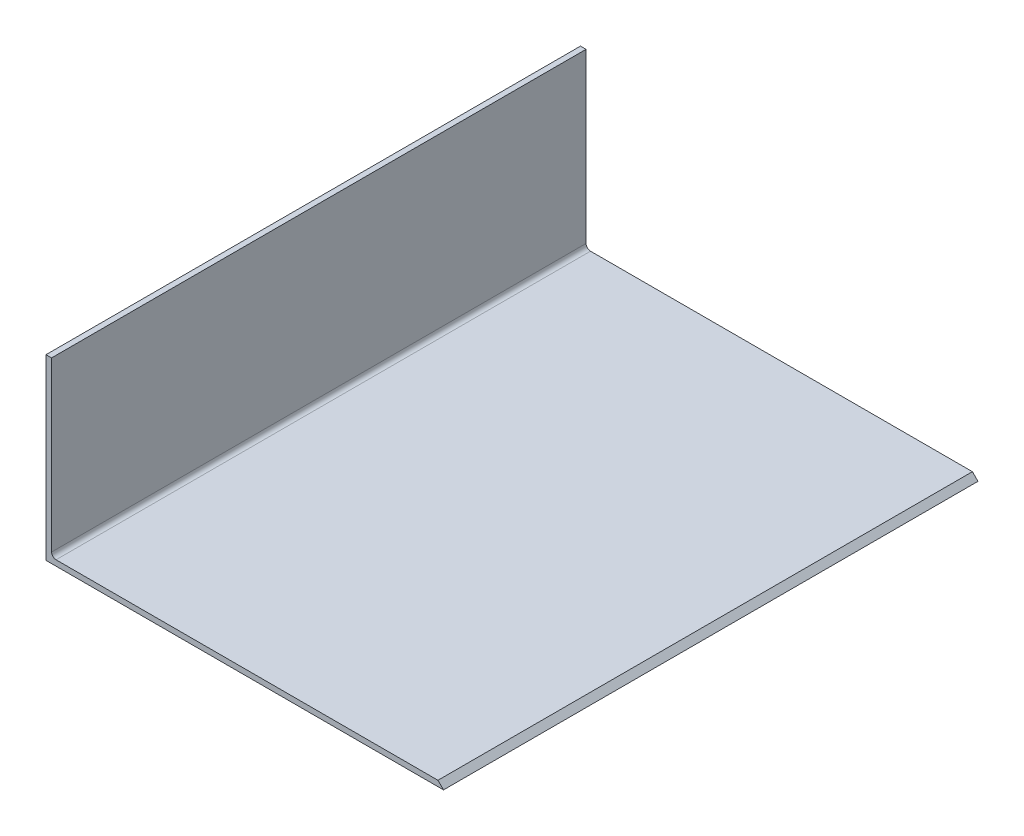
SolidWorks part; units mm, degrees
ref_plane "Front Plane" through (0, 0, 0) normal (0, 0, 1) x (1, 0, 0)
ref_plane "Top Plane" through (0, 0, 0) normal (0, 1, 0) x (1, 0, 0)
ref_plane "Right Plane" through (0, 0, 0) normal (1, 0, 0) x (0, 0, -1)
sketch "Sketch1" plane through (0, 0, 0) normal (0, 0, 1) x (1, 0, 0)
  line L1 (0, 0) -> (3.175, 0)
  line L2 (0, 0) -> (0, 98.425)
  line L3 (0, 98.425) -> (3.175, 98.425)
  line L4 (3.175, 0) -> (3.175, 98.425)
  line L5 (0, 0) -> (228.6, 0)
  line L6 (0, 0) -> (0, -3.175)
  line L7 (0, -3.175) -> (228.6, -3.175)
  line L8 (228.6, 0) -> (228.6, -3.175)
  arc A1 (3.175, 2.54) -> (5.715, 0) centre (5.715, 2.54) ccw
  dimension "D4" = 2.54
  dimension "D1" = 3.175
  dimension "D2" = 228.6
  dimension "D3" = 101.6
extrude "Boss-Extrude1" add sketch "Sketch1" along normal mid plane 304.8 contours L8 L5 L1 L6 L7 | L1 L4 L3 L2 | A1 L4 L5 region at (1.5875, 49.2125, 0) region at (114.3, -1.5875, 0) region at (3.7424, 0.5674, 0)
chamfer "Chamfer1" distance 5.08 angle 45 1 edges at (228.6, 0, 0)
